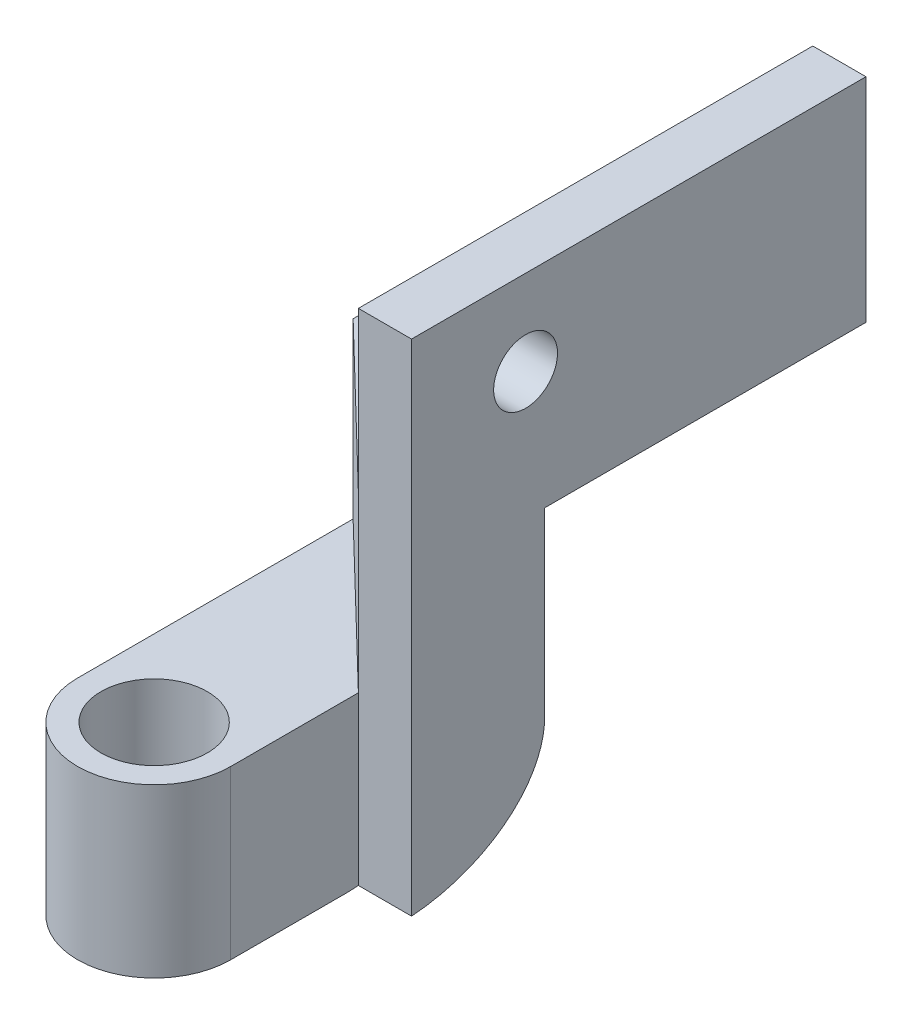
SolidWorks part; units mm, degrees
ref_plane "Front Plane" through (0, 0, 0) normal (0, 0, 1) x (1, 0, 0)
ref_plane "Top Plane" through (0, 0, 0) normal (0, 1, 0) x (1, 0, 0)
ref_plane "Right Plane" through (0, 0, 0) normal (1, 0, 0) x (0, 0, -1)
sketch "Croquis1" plane through (0, 0, 0) normal (0, 1, 0) x (1, 0, 0)
  line L3 (-3.6, 27.36) -> (-3.6, 0)
  line L4 (3.6, 0) -> (3.6, 27.36)
  line L5 (3.6, 27.36) -> (-3.6, 27.36)
  line L6 (-3.6, 12.953) -> (3.6, 6)
  line L7 (0, 0) -> (-2.5, 0) construction
  line L8 (-3.6, 19.2087) -> (3.6, 12.2557)
  arc A3 (-3.6, 0) -> (3.6, 0) centre (0, 0) ccw
  circle A4 centre (0, 0) radius 2.5
  circle A5 centre (-0.4, 21.36) radius 1.5
  point P13 (-6.92, 27.36)
  point P14 (-5.1047, 27.36)
  point P15 (0, 0)
  dimension "D1" = 3.6
  dimension "D6" = 5
  dimension "D10" = 3
  dimension "D2" = 27.36
  dimension "D7" = 44
  dimension "D8" = 6
  dimension "D9" = 4.5
  dimension "D11" = 6
  dimension "D12" = 4
extrude "Saliente-Extruir1" add sketch "Croquis1" against normal blind 2.5 contours L3 L8 L4 L5 A5 | L8 L3 L6 L4 region at (0, 0, -27.1927) region at (0, 0, -12.6043)
extrude "Saliente-Extruir2" add sketch "Croquis1<4>" against normal blind 7.87 from offset 8.15 separate body contours L3 A3 L4 L6 A4 region at (-0.4356, 0, -4.4478) offset against normal yes
sketch "Croquis1<4>" plane through (0, 0, 0) normal (0, 1, 0) x (1, 0, 0) same geometry as "Croquis1"
extrude "Saliente-Extruir3" add sketch "Croquis1<5>" against normal up to surface (16.02 mm away) contours L8 L3 L6 L4 region at (0, 0, -12.6043) up to face at (0, -16.02, 2.5)
sketch "Croquis1<5>" plane through (0, 0, 0) normal (0, 1, 0) x (1, 0, 0) same geometry as "Croquis1"
fillet "Redondeo1" radius 5 1 edges at (0, -16.02, -15.7322)
sketch "Croquis3" plane through (3.6, 0, 0) normal (1, 0, 0) x (0, 0, -1)
  line L0 (6, -8.15) -> (6, -15.9949)
  line L1 (27.36, 7.5) -> (6, 7.5)
  line L8 (0, -16.02) -> (5.3049, -16.02)
  line L9 (12.2557, -11.02) -> (12.2557, -2.5)
  line L10 (12.2557, -2.5) -> (27.36, -2.5)
  line L11 (27.36, -2.5) -> (27.36, 0)
  line L12 (27.36, 0) -> (6, 0)
  line L13 (6, 0) -> (6, -8.15)
  line L14 (6, -8.15) -> (0, -8.15)
  line L15 (0, -8.15) -> (0, -16.02)
  line L16 (0, -16.02) -> (5.3049, -16.02)
  line L17 (12.2557, -11.02) -> (12.2557, -2.5)
  line L18 (12.2557, -2.5) -> (27.36, -2.5)
  line L19 (27.36, -2.5) -> (27.36, 7.5)
  line L21 (6, 7.5) -> (6, -8.15)
  line L22 (6, -8.15) -> (0, -8.15)
  line L23 (0, -8.15) -> (0, -16.02)
  circle A0 centre (11.36, 3.5) radius 1.5
  ellipse E1 centre (5.3049, -11.02) end of major axis (12.2557, -11.02) minor radius 5 (5.3049, -16.02) -> (12.2557, -11.02) ccw
  ellipse E2 centre (5.3049, -11.02) end of major axis (12.2557, -11.02) minor radius 5 (5.3049, -16.02) -> (12.2557, -11.02) ccw
  ellipse M2 centre (5.3049, -11.02) end of major axis (12.2557, -11.02) minor radius 5 (5.3049, -16.02) -> (12.2557, -11.02) ccw
  line M3 (12.2557, -11.02) -> (12.2557, -2.5)
  line M4 (12.2557, -2.5) -> (27.36, -2.5)
  line M5 (27.36, -2.5) -> (27.36, 0)
  line M6 (27.36, 0) -> (6, 0)
  line M7 (6, 0) -> (6, -8.15)
  dimension "D5" = 3
  dimension "D2" = 10
  dimension "D3" = 16
  dimension "D4" = 4
  dimension "D1" = 0
extrude "Saliente-Extruir4" add sketch "Croquis3" along normal blind 2.5 contours L0 M7 M2 M3 M4 M5 M6 | L1 L21 L19 A0 M6 region at (3.6, -5.6608, -12.1274) region at (3.6, 3.7615, -16.9256)
equation "\"D1@Saliente-Extruir2\"=7.87"
